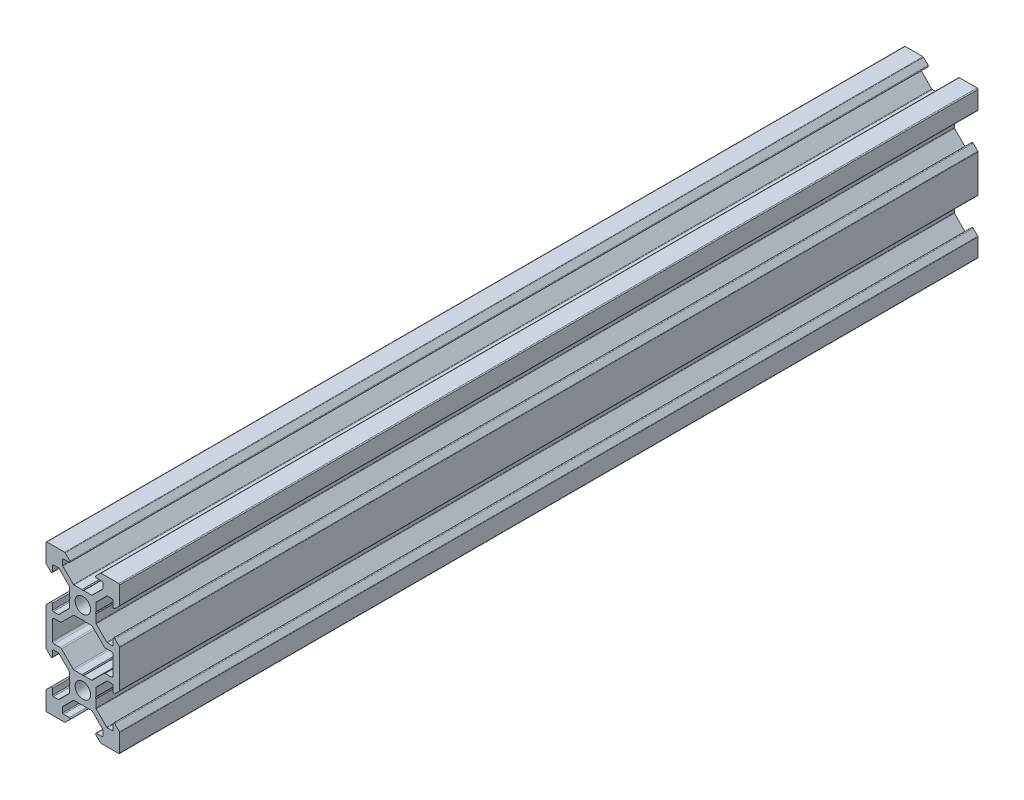
SolidWorks part; units mm, degrees
ref_plane "Front Plane" through (0, 0, 0) normal (0, 0, 1) x (1, 0, 0)
ref_plane "Top Plane" through (0, 0, 0) normal (0, 1, 0) x (1, 0, 0)
ref_plane "Right Plane" through (0, 0, 0) normal (1, 0, 0) x (0, 0, -1)
sketch "Sketch1" plane through (0, 0, 0) normal (0, 0, 1) x (1, 0, 0)
  line L0 (3.5607, 3.5607) -> (10.6317, 10.6317) construction
  line L1 (2.5, -3.5607) -> (-2.5, -3.5607)
  line L2 (3.5607, -2.5) -> (3.5607, 2.5)
  line L3 (2.5, 3.5607) -> (-2.5, 3.5607)
  line L4 (-3.5607, -2.5) -> (-3.5607, 2.5)
  line L5 (3.5607, -3.5607) -> (-3.5607, 3.5607) construction
  line L6 (3.5607, 3.5607) -> (-3.5607, -3.5607) construction
  line L7 (2.5, 3.5607) -> (5.5, 6.5607)
  line L8 (5.5, 6.5607) -> (5.5, 8.2521)
  line L9 (5.5, 8.2521) -> (3.1, 8.2521)
  line L10 (3.1, 8.2521) -> (4.8479, 10)
  line L11 (4.8479, 10) -> (10, 10)
  line L12 (3.5607, 2.5) -> (6.5607, 5.5)
  line L13 (6.5607, 5.5) -> (8.2521, 5.5)
  line L14 (8.2521, 5.5) -> (8.2521, 3.1)
  line L15 (8.2521, 3.1) -> (10, 4.8479)
  line L16 (10, 4.8479) -> (10, 10)
  line L17 (0, -55) -> (0, 55) construction
  line L18 (-3.5607, 3.5607) -> (-10.6317, 10.6317) construction
  line L19 (-10, 4.8479) -> (-10, 10)
  line L20 (-8.2521, 3.1) -> (-10, 4.8479)
  line L21 (-8.2521, 5.5) -> (-8.2521, 3.1)
  line L22 (-6.5607, 5.5) -> (-8.2521, 5.5)
  line L23 (-3.5607, 2.5) -> (-6.5607, 5.5)
  line L24 (-4.8479, 10) -> (-10, 10)
  line L25 (-3.1, 8.2521) -> (-4.8479, 10)
  line L26 (-5.5, 8.2521) -> (-3.1, 8.2521)
  line L27 (-5.5, 6.5607) -> (-5.5, 8.2521)
  line L28 (-2.5, 3.5607) -> (-5.5, 6.5607)
  line L29 (-8.2521, -7) -> (-5.9393, -7)
  line L30 (55, 0) -> (-55, 0) construction
  line L31 (-3.5607, -3.5607) -> (-10.6317, -10.6317) construction
  line L32 (3.5607, -3.5607) -> (10.6317, -10.6317) construction
  line L33 (-2.5, -3.5607) -> (-5.5, -6.5607)
  line L34 (-5.5, -6.5607) -> (-5.9393, -7)
  line L35 (5.5, -6.5607) -> (5.9393, -7)
  line L36 (8.2521, -7) -> (5.9393, -7)
  line L37 (-12.2633, -10) -> (14.5346, -10) construction
  line L38 (-3.5607, -2.5) -> (-6.5607, -5.5)
  line L39 (-6.5607, -5.5) -> (-8.2521, -5.5)
  line L40 (-8.2521, -5.5) -> (-8.2521, -3.1)
  line L41 (-8.2521, -3.1) -> (-10, -4.8479)
  line L42 (-10, -4.8479) -> (-10, -7)
  line L43 (10, -4.8479) -> (10, -7)
  line L44 (8.2521, -3.1) -> (10, -4.8479)
  line L45 (8.2521, -5.5) -> (8.2521, -3.1)
  line L46 (6.5607, -5.5) -> (8.2521, -5.5)
  line L47 (3.5607, -2.5) -> (6.5607, -5.5)
  line L48 (-3.5607, -23.5607) -> (-10.6317, -30.6317) construction
  line L49 (3.5607, -23.5607) -> (-3.5607, -16.4393) construction
  line L50 (3.5607, -16.4393) -> (-3.5607, -23.5607) construction
  line L51 (3.5607, -23.5607) -> (10.6317, -30.6317) construction
  line L52 (2.5, -3.5607) -> (5.5, -6.5607)
  line L53 (2.5, -16.4393) -> (5.5, -13.4393)
  line L54 (3.5607, -17.5) -> (6.5607, -14.5)
  line L55 (6.5607, -14.5) -> (8.2521, -14.5)
  line L56 (8.2521, -14.5) -> (8.2521, -16.9)
  line L57 (8.2521, -16.9) -> (10, -15.1521)
  line L58 (10, -15.1521) -> (10, -13)
  line L59 (-10, -15.1521) -> (-10, -13)
  line L60 (-8.2521, -16.9) -> (-10, -15.1521)
  line L61 (-8.2521, -14.5) -> (-8.2521, -16.9)
  line L62 (-6.5607, -14.5) -> (-8.2521, -14.5)
  line L63 (-3.5607, -17.5) -> (-6.5607, -14.5)
  line L64 (8.2521, -13) -> (5.9393, -13)
  line L65 (5.5, -13.4393) -> (5.9393, -13)
  line L66 (-5.5, -13.4393) -> (-5.9393, -13)
  line L67 (-2.5, -16.4393) -> (-5.5, -13.4393)
  line L68 (-8.2521, -13) -> (-5.9393, -13)
  line L69 (-2.5, -23.5607) -> (-5.5, -26.5607)
  line L70 (-5.5, -26.5607) -> (-5.5, -28.2521)
  line L71 (-5.5, -28.2521) -> (-3.1, -28.2521)
  line L72 (-3.1, -28.2521) -> (-4.8479, -30)
  line L73 (-4.8479, -30) -> (-10, -30)
  line L74 (-3.5607, -22.5) -> (-6.5607, -25.5)
  line L75 (-6.5607, -25.5) -> (-8.2521, -25.5)
  line L76 (-8.2521, -25.5) -> (-8.2521, -23.1)
  line L77 (-8.2521, -23.1) -> (-10, -24.8479)
  line L78 (-10, -24.8479) -> (-10, -30)
  line L79 (10, -24.8479) -> (10, -30)
  line L80 (8.2521, -23.1) -> (10, -24.8479)
  line L81 (8.2521, -25.5) -> (8.2521, -23.1)
  line L82 (6.5607, -25.5) -> (8.2521, -25.5)
  line L83 (3.5607, -22.5) -> (6.5607, -25.5)
  line L84 (4.8479, -30) -> (10, -30)
  line L85 (3.1, -28.2521) -> (4.8479, -30)
  line L86 (5.5, -28.2521) -> (3.1, -28.2521)
  line L87 (5.5, -26.5607) -> (5.5, -28.2521)
  line L88 (2.5, -23.5607) -> (5.5, -26.5607)
  line L89 (-3.5607, -17.5) -> (-3.5607, -22.5)
  line L90 (2.5, -23.5607) -> (-2.5, -23.5607)
  line L91 (3.5607, -17.5) -> (3.5607, -22.5)
  line L92 (2.5, -16.4393) -> (-2.5, -16.4393)
  line L93 (-10, -7) -> (-10, -13)
  line L94 (-8.2521, -13) -> (-8.2521, -7)
  line L95 (8.2521, -13) -> (8.2521, -7)
  line L96 (10, -7) -> (10, -13)
  circle A0 centre (0, 0) radius 2.1
  circle A1 centre (0, -20) radius 2.1
  point P0 (0, 0)
  point P102 (0, -20)
  dimension "D10" = 4.2
  dimension "D11" = 4.2
  dimension "D1" = 1.5
  dimension "D2" = 10
  dimension "D3" = 20
  dimension "D4" = 6.2
  dimension "D5" = 11
  dimension "D6" = 45
  dimension "D7" = 1.5
  dimension "D8" = 10
  dimension "D9" = 5
extrude "Boss-Extrude1" add sketch "Sketch1" along normal blind 233.04
fillet "Fillet1" radius 0.25 64 edges at (5.5, 6.5607, 116.52) (5.5, 8.2521, 116.52) (3.1, 8.2521, 116.52) (4.8479, 10, 116.52) (10, 10, 116.52) (10, 4.8479, 116.52) (8.2521, 3.1, 116.52) (8.2521, 5.5, 116.52) (6.5607, 5.5, 116.52) (3.5607, 2.5, 116.52) (3.5607, -2.5, 116.52) (6.5607, -5.5, 116.52) (8.2521, -5.5, 116.52) (8.2521, -3.1, 116.52) (10, -4.8479, 116.52) (10, -15.1521, 116.52) (8.2521, -16.9, 116.52) (8.2521, -14.5, 116.52) (6.5607, -14.5, 116.52) (3.5607, -17.5, 116.52) (3.5607, -22.5, 116.52) (6.5607, -25.5, 116.52) (8.2521, -25.5, 116.52) (8.2521, -23.1, 116.52) (10, -24.8479, 116.52) (10, -30, 116.52) (4.8479, -30, 116.52) (3.1, -28.2521, 116.52) (5.5, -28.2521, 116.52) (5.5, -26.5607, 116.52) (2.5, -23.5607, 116.52) (-2.5, -23.5607, 116.52) (-5.5, -26.5607, 116.52) (-5.5, -28.2521, 116.52) (-3.1, -28.2521, 116.52) (-4.8479, -30, 116.52) (-10, -30, 116.52) (-10, -24.8479, 116.52) (-8.2521, -23.1, 116.52) (-8.2521, -25.5, 116.52) (-6.5607, -25.5, 116.52) (-3.5607, -22.5, 116.52) (-3.5607, -17.5, 116.52) (-6.5607, -14.5, 116.52) (-8.2521, -14.5, 116.52) (-8.2521, -16.9, 116.52) (-10, -15.1521, 116.52) (-10, -4.8479, 116.52) (-8.2521, -3.1, 116.52) (-8.2521, -5.5, 116.52) (-6.5607, -5.5, 116.52) (-3.5607, -2.5, 116.52) (-3.5607, 2.5, 116.52) (-6.5607, 5.5, 116.52) (-8.2521, 5.5, 116.52) (-8.2521, 3.1, 116.52) (-10, 4.8479, 116.52) (-10, 10, 116.52) (-4.8479, 10, 116.52) (-5.5, 8.2521, 116.52) (-5.5, 6.5607, 116.52) (-2.5, 3.5607, 116.52) (2.5, 3.5607, 116.52) (-3.1, 8.2521, 116.52)
fillet "Fillet2" radius 0.5 12 edges at (-5.9393, -7, 116.52) (-8.2521, -7, 116.52) (-8.2521, -13, 116.52) (-5.9393, -13, 116.52) (-2.5, -16.4393, 116.52) (2.5, -16.4393, 116.52) (8.2521, -7, 116.52) (5.9393, -7, 116.52) (2.5, -3.5607, 116.52) (-2.5, -3.5607, 116.52) (5.9393, -13, 116.52) (8.2521, -13, 116.52)
sketch "Sketch2" plane through (0, 0, 233.04) normal (0, 0, 1) x (1, 0, 0)
  line L4 (0, 3.5607) -> (0, 3.1447) construction
  line L5 (2.3964, 3.5607) -> (-2.3964, 3.5607) construction
  line L6 (0, 3.399) -> (-0.2423, 3.5607)
  line L7 (0, 3.399) -> (0.2423, 3.5607)
  line L8 (-0.2423, 3.5607) -> (0.2423, 3.5607)
  line L9 (55, 0) -> (-55, 0) construction
  line L10 (0, -3.5607) -> (0, -3.1447) construction
  line L11 (0, -3.399) -> (0.2423, -3.5607)
  line L12 (0, -3.399) -> (-0.2423, -3.5607)
  line L13 (-0.2423, -3.5607) -> (0.2423, -3.5607)
  line L14 (0, 0) -> (-4.0856, 4.0856) construction
  line L15 (-8.2521, -10) -> (4.1581, -10) construction
  line L16 (-8.2521, -7.5) -> (-8.2521, -12.5) construction
  line L17 (3.5607, 0) -> (3.1447, 0) construction
  line L18 (3.5607, 0.2423) -> (3.5607, -0.2423)
  line L19 (3.399, 0) -> (3.5607, 0.2423)
  line L20 (3.399, 0) -> (3.5607, -0.2423)
  line L21 (-3.5607, 0) -> (-3.1447, 0) construction
  line L22 (-3.5607, 0.2423) -> (-3.5607, -0.2423)
  line L23 (-3.399, 0) -> (-3.5607, -0.2423)
  line L24 (-3.399, 0) -> (-3.5607, 0.2423)
  line L25 (-3.5607, -20) -> (-3.1447, -20) construction
  line L26 (3.5607, -20) -> (3.1447, -20) construction
  line L27 (0, -20) -> (-4.0856, -24.0856) construction
  line L28 (0, -16.4393) -> (0, -16.8553) construction
  line L29 (0, -23.5607) -> (0, -23.1447) construction
  line L30 (-3.399, -20) -> (-3.5607, -20.2423)
  line L31 (-3.399, -20) -> (-3.5607, -19.7577)
  line L32 (-3.5607, -20.2423) -> (-3.5607, -19.7577)
  line L33 (3.399, -20) -> (3.5607, -19.7577)
  line L34 (3.399, -20) -> (3.5607, -20.2423)
  line L35 (3.5607, -20.2423) -> (3.5607, -19.7577)
  line L36 (-0.2423, -16.4393) -> (0.2423, -16.4393)
  line L37 (0, -16.601) -> (-0.2423, -16.4393)
  line L38 (0, -16.601) -> (0.2423, -16.4393)
  line L39 (-0.2423, -23.5607) -> (0.2423, -23.5607)
  line L40 (0, -23.399) -> (0.2423, -23.5607)
  line L41 (0, -23.399) -> (-0.2423, -23.5607)
extrude "Cut-Extrude1" cut sketch "Sketch2" against normal through all
